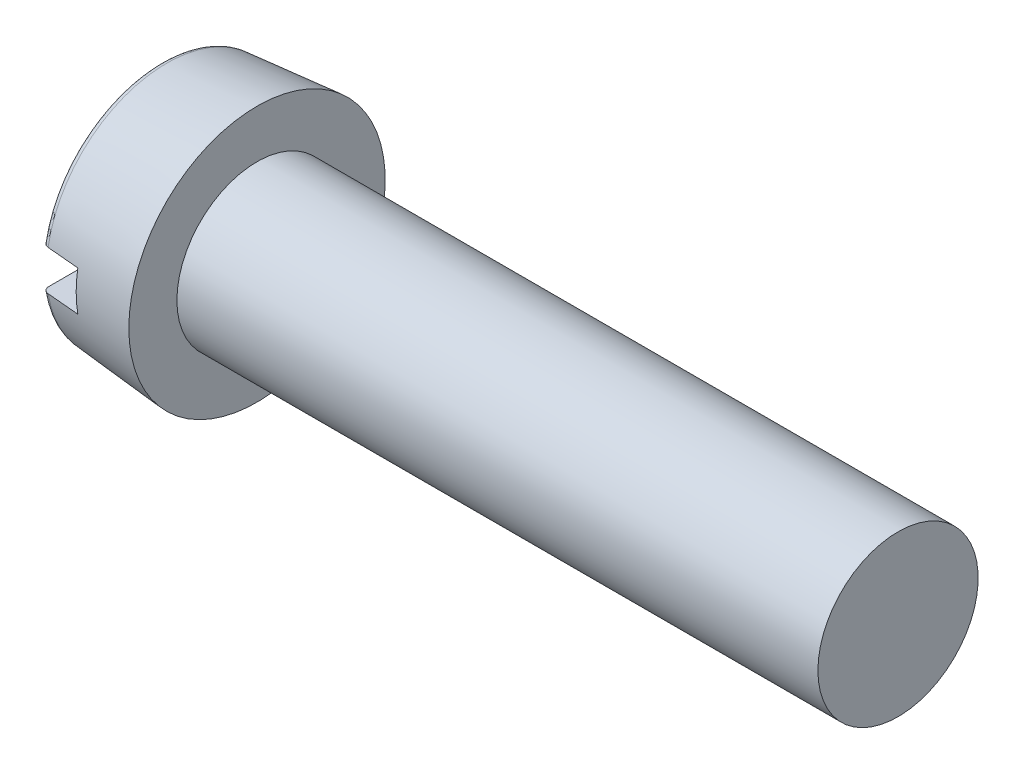
SolidWorks part; units mm, degrees
ref_plane "Front Plane" through (0, 0, 0) normal (0, 0, 1) x (1, 0, 0)
ref_plane "Top Plane" through (0, 0, 0) normal (0, 1, 0) x (1, 0, 0)
ref_plane "Right Plane" through (0, 0, 0) normal (1, 0, 0) x (0, 0, -1)
sketch "BodySke" plane through (0, 0, 0) normal (0, 0, 1) x (1, 0, 0)
  line L0 (0, 0) -> (111.3824, 0) construction
  line L1 (0, 0) -> (0, 7.4751)
  line L2 (0, 7.4751) -> (6, 8)
  line L3 (6, 8) -> (6, 5)
  line L4 (6, 5) -> (46, 5)
  line L5 (46, 5) -> (46, 0)
  line L6 (7.5, 8.824) -> (7.5, -5.8939) construction
  line L7 (0, 0) -> (46, 0)
  line L8 (8, 8.824) -> (8, -4.958) construction
  point P10 (46, 4.172)
  dimension "Thread_minor" = 8.344
  dimension "Advance" = 1.5
revolve "BaseBody" add sketch "BodySke" angle 360 about L0
cosmetic thread "ThreadCosmetic" [suppressed] parameters "Thread_minor"=8.344
fillet "Fillet1" radius 0.4 1 edges at (0, 0, 7.4751)
sketch "SlotSke" plane through (0, 0, 0) normal (-1, 0, 0) x (0, 0, 1)
  line L1 (-8, 1.25) -> (8, 1.25)
  line L2 (-8, 1.25) -> (-8, -1.25)
  line L3 (-8, -1.25) -> (8, -1.25)
  line L4 (8, 1.25) -> (8, -1.25)
  dimension "D1" = 16
  dimension "D2" = 8
  dimension "D3" = 1.25
extrude "Slot" cut sketch "SlotSke" against normal blind 2.4
sketch "ThdSchSke" plane through (0, 0, 0) normal (0, 0, 1) x (1, 0, 0)
  line L0 (0, 0) -> (55.1256, 0) construction
  line L1 (0, 0) -> (111.3824, 0) construction
  line L2 (45.522, 5) -> (45.522, 5.9561)
  line L3 (45.522, 5.9561) -> (46.478, 5.9561)
  line L4 (46.478, 5.9561) -> (46.478, 5)
  line L5 (46.478, 5) -> (46, 4.172)
  line L6 (46, 4.172) -> (45.522, 5)
  line L7 (6, 5) -> (46, 5) construction
  line L13 (46, 5) -> (46, 0) construction
revolve "ThreadSchematic" [suppressed] cut sketch "ThdSchSke" angle 360 about L0
pattern_linear "ThdSchPat" [suppressed] count 25 along (-1, 0, 0) of bodies 103
equation "\"Thread_minor@ThreadCosmetic\" = \"Thread_minor@BodySke\""
equation "\"D1@SlotSke\" = \"Head_dia@BodySke\""
equation "\"D2@SlotSke\" = \"D1@SlotSke\" / 2"
equation "\"D3@SlotSke\" = \"Slot_width@SlotSke\" / 2"
equation "\"Advance@ThdSchPat\" = \"Advance@BodySke\""
equation "\"D1@ThdSchPat\" =  int( \"Thread_length@BodySke\" / \"Advance@ThdSchPat\" ) "
